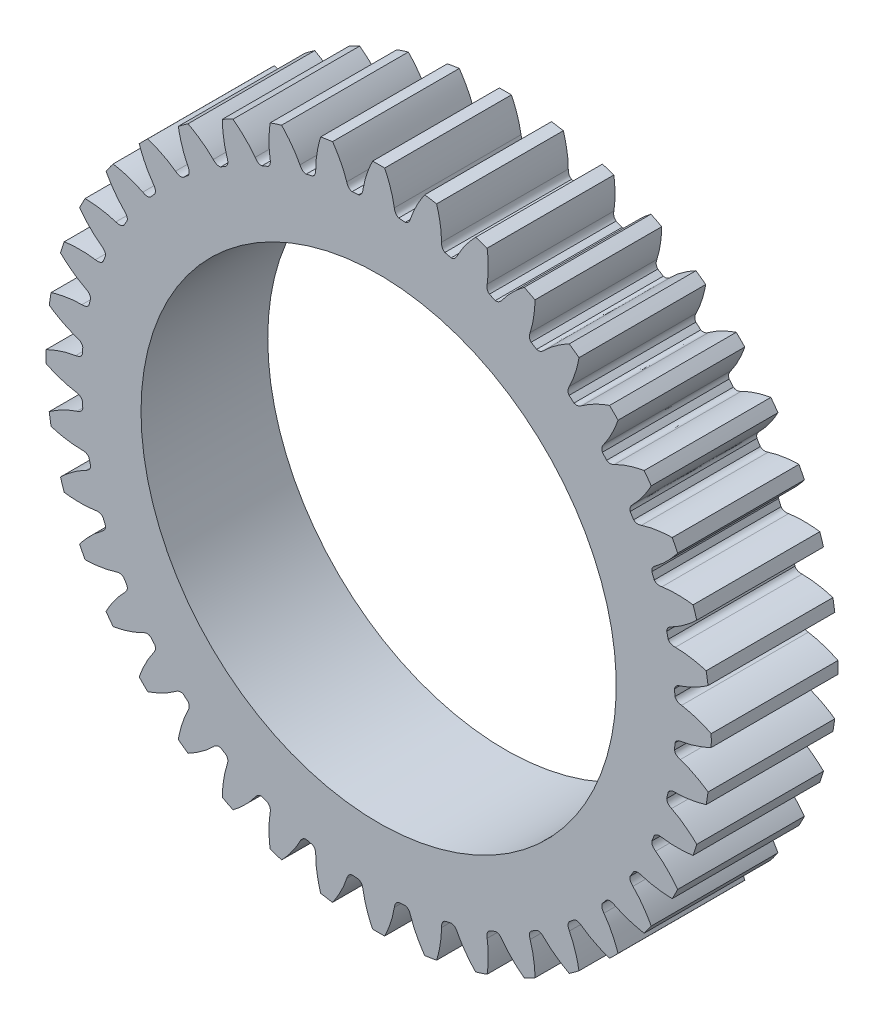
SolidWorks part; units mm, degrees
ref_plane "정면" through (0, 0, 0) normal (0, 0, 1) x (1, 0, 0)
ref_plane "윗면" through (0, 0, 0) normal (0, 1, 0) x (1, 0, 0)
ref_plane "우측면" through (0, 0, 0) normal (1, 0, 0) x (0, 0, -1)
sketch "스케치1" plane through (0, 0, 0) normal (0, 0, 1) x (1, 0, 0)
  circle A0 centre (0, 0) radius 18.75
extrude "보스-돌출1" add sketch "스케치1" along normal blind 8
sketch "스케치2" plane through (0, 0, 0) normal (0, 0, -1) x (-1, 0, 0)
  arc A0 (-0.3803, 20.9939) -> (0.3803, 20.9938) centre (-0.0021, -0.0027)
  arc A1 (-1.3368, 18.6739) -> (1.3212, 18.6747) centre (-0.0021, -0.0027)
  spline S0 degree 3 poles (-0.9906, 19.1225) (-0.9749, 19.2322) (-0.942, 19.4089) (-0.8815, 19.6593) (-0.8181, 19.8843) (-0.7379, 20.1325) (-0.6001, 20.5091) (-0.4753, 20.7976) (-0.3803, 20.9939) knots 0 0 0 0 0.168175 0.272795 0.391101 0.523096 0.668778 1 1 1 1
  spline S1 degree 3 poles (0.9906, 19.1225) (0.9749, 19.2322) (0.942, 19.4089) (0.8815, 19.6593) (0.8181, 19.8843) (0.7379, 20.1325) (0.6001, 20.5091) (0.4753, 20.7975) (0.3803, 20.9938) knots 0 0 0 0 0.168181 0.272804 0.391115 0.523114 0.668801 1 1 1 1
  spline S2 degree 3 poles (-0.9906, 19.1225) (-0.9964, 19.0817) (-1.0082, 19.0215) (-1.0338, 18.9439) (-1.0596, 18.8867) (-1.096, 18.829) (-1.1775, 18.7397) (-1.2753, 18.7074) (-1.3368, 18.6739) knots 0 0 0 0 0.205092 0.304337 0.406051 0.516142 0.642853 1 1 1 1
  spline S3 degree 3 poles (0.9906, 19.1225) (0.9964, 19.0817) (1.0082, 19.0215) (1.0338, 18.9439) (1.0596, 18.8867) (1.096, 18.829) (1.1741, 18.743) (1.2667, 18.712) (1.3212, 18.6747) knots 0 0 0 0 0.210012 0.311637 0.415791 0.528523 0.658274 1 1 1 1
extrude "보스-돌출6" add sketch "스케치2" against normal blind 8 contours S0 A0 S1 S3 A1 S2
pattern_circular "원형 패턴1" count 40 over 360 about axis through (0, 0, 8) along (0, 0, -1) of "보스-돌출6"
sketch "스케치3" plane through (0, 0, 0) normal (0, 0, -1) x (-1, 0, 0)
  circle A0 centre (0, 0) radius 15
extrude "컷-돌출1" cut sketch "스케치3" against normal blind 8 contours A0
